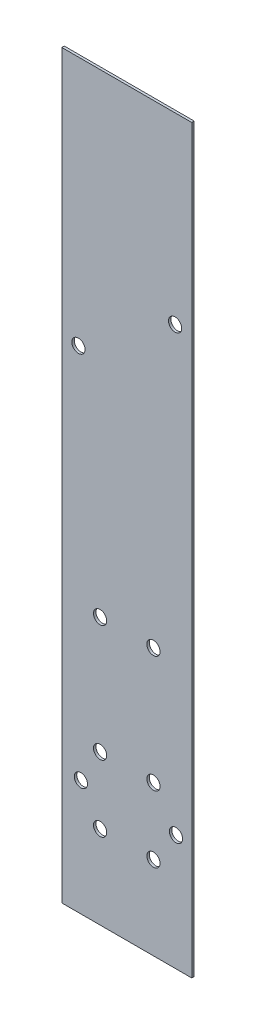
SolidWorks part; units mm, degrees
material "Acrylic (Medium-high impact)"
ref_plane "Front Plane" through (0, 0, 0) normal (0, 0, 1) x (1, 0, 0)
ref_plane "Top Plane" through (0, 0, 0) normal (0, 1, 0) x (1, 0, 0)
ref_plane "Right Plane" through (0, 0, 0) normal (1, 0, 0) x (0, 0, -1)
sketch "Sketch1" plane through (0, 0, 0) normal (0, 0, 1) x (1, 0, 0)
  line L1 (0, 222.25) -> (39, 222.25)
  line L2 (0, 222.25) -> (0, 0)
  line L3 (0, 0) -> (39, 0)
  line L4 (39, 222.25) -> (39, 0)
  dimension "D1" = 222.25
  dimension "D2" = 39
base flange "Base-Flange1" sketch "Sketch1" thickness 0.7366 reverse thickness direction no parameters "D1"=0.7366
sketch "Sketch2" plane through (0, 0, 0) normal (0, 0, 1) x (1, 0, 0)
  line L0 (0, 222.25) -> (0, 0) construction
  line L1 (0, 0) -> (39, 0) construction
  circle A2 centre (5, 147.25) radius 1.9844
  circle A7 centre (5.7366, 34.75) radius 1.9844 construction
  circle A8 centre (34.2634, 34.75) radius 1.9844 construction
  circle A11 centre (34, 167.25) radius 1.9844
  circle A12 centre (27.5, 80) radius 1.9844
  circle A13 centre (11.5, 80) radius 1.9844
  circle A14 centre (11.5, 45) radius 1.9844
  circle A15 centre (27.5, 45) radius 1.9844
  circle A16 centre (5.7366, 34.75) radius 1.9844
  circle A17 centre (34.2634, 34.75) radius 1.9844
  circle A18 centre (27.5, 25) radius 1.9844
  circle A19 centre (11.5, 25) radius 1.9844
  dimension "D1" = 5
  dimension "D2" = 11.5
  dimension "D3" = 27.5
  dimension "D4" = 34
  dimension "D5" = 25
  dimension "D6" = 45
  dimension "D7" = 80
  dimension "D8" = 147.25
  dimension "D9" = 167.25
extrude "Cut-Extrude1" cut sketch "Sketch2" against normal blind 10 normal cut yes
sketch "Bend-Lines1" [suppressed] plane through (0, 0, 0) normal (0, 1, 0) x (1, 0, 0)
sketch "Bounding-Box1" [suppressed] plane through (0, 0, 0) normal (0, 1, 0) x (1, 0, 0)
sheet metal parameters "Sheet-Metal3" thickness 0.7366 parameters "D1"=0.7366
flat pattern "Flat-Pattern3" [suppressed]
sketch "Bend-Lines2" plane through (0, 0, 0) normal (0, 1, 0) x (1, 0, 0)
sketch "Bounding-Box2" [suppressed] plane through (0, 0, 0) normal (0, 1, 0) x (1, 0, 0)
sheet metal parameters "Sheet-Metal4" thickness 0.7366 parameters "D1"=0.7366
flat pattern "Flat-Pattern3"
sketch "Bend-Lines2" plane through (0, 0, 0) normal (0, 1, 0) x (1, 0, 0)
sketch3d "Bounding-Box2" [suppressed]
  line L0 (39, 222.25, 0) -> (39, 0, 0) construction
  line L1 (0, 222.25, 0) -> (0, 0, 0) construction
  line L2 (39, 222.25, 0) -> (0, 222.25, 0) construction
  line L3 (39, 0, 0) -> (0, 0, 0) construction
